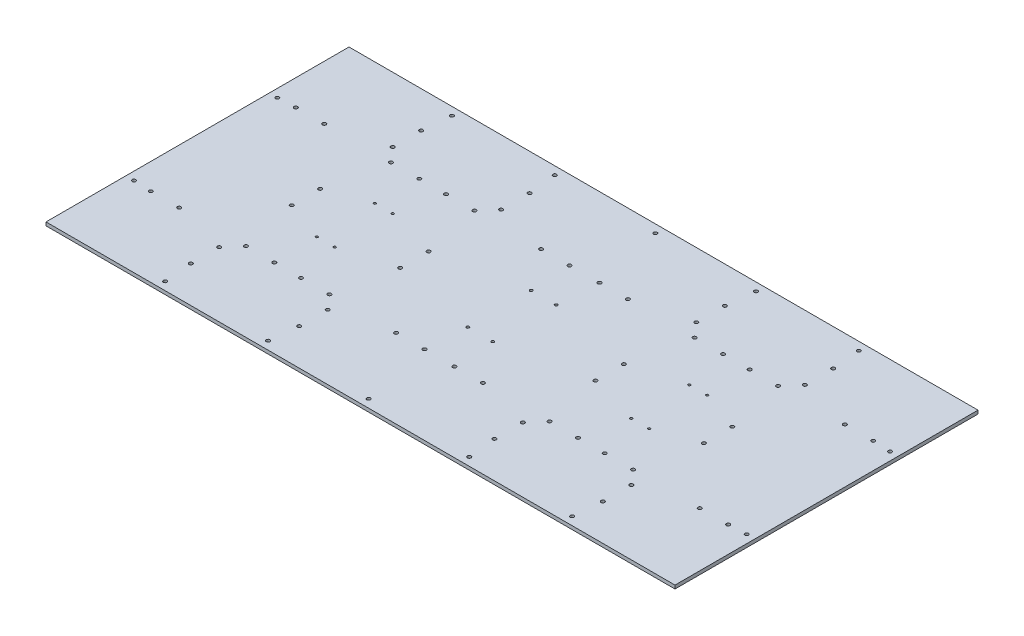
SolidWorks part; units mm, degrees
ref_plane "Front Plane" through (0, 0, 0) normal (0, 0, 1) x (1, 0, 0)
ref_plane "Top Plane" through (0, 0, 0) normal (0, 1, 0) x (1, 0, 0)
ref_plane "Right Plane" through (0, 0, 0) normal (1, 0, 0) x (0, 0, -1)
sketch "Sketch1" plane through (0, 0, 0) normal (0, 1, 0) x (1, 0, 0)
  line L0 (0, 139.7) -> (0, -139.7) construction
  line L1 (-290, 139.7) -> (290, 139.7)
  line L2 (-290, 139.7) -> (-290, -139.7)
  line L3 (-290, -139.7) -> (290, -139.7)
  line L4 (290, 139.7) -> (290, -139.7)
  line L5 (-290, 139.7) -> (290, -139.7) construction
  line L6 (-290, -139.7) -> (290, 139.7) construction
  line L7 (-282.5, 132.2) -> (282.5, 132.2) construction
  line L8 (-282.5, 132.2) -> (-282.5, -132.2) construction
  line L9 (-282.5, -132.2) -> (282.5, -132.2) construction
  line L10 (282.5, 132.2) -> (282.5, -132.2) construction
  line L11 (-282.5, 132.2) -> (282.5, -132.2) construction
  line L12 (-282.5, -132.2) -> (282.5, 132.2) construction
  line L13 (-290, 0) -> (290, 0) construction
  line L14 (282.5, 132.2) -> (282.5, -132.2) construction
  circle A0 centre (-282.5, 66.1) radius 1.65
  circle A1 centre (-187.6333, 132.2) radius 1.65
  circle A2 centre (-92.7667, 132.2) radius 1.65
  circle A3 centre (-282.5, -66.1) radius 1.65
  circle A4 centre (-92.7667, -132.2) radius 1.65
  circle A5 centre (-187.6333, -132.2) radius 1.65
  circle A6 centre (187.6333, -132.2) radius 1.65
  circle A7 centre (92.7667, -132.2) radius 1.65
  circle A8 centre (92.7667, 132.2) radius 1.65
  circle A9 centre (187.6333, 132.2) radius 1.65
  circle A10 centre (282.5, -66.1) radius 1.65
  circle A11 centre (282.5, 66.1) radius 1.65
  circle A12 centre (0, 132.2) radius 1.65
  circle A13 centre (0, -132.2) radius 1.65
  point P0 (0, 0)
  point P6 (0, 0)
  dimension "D5" = 3.3
  dimension "D6" = 3.3
  dimension "D7" = 3.3
  dimension "D12" = 3.3
  dimension "D13" = 3.3
  dimension "D1" = 580
  dimension "D2" = 279.4
  dimension "D3" = 7.5
  dimension "D4" = 7.5
  dimension "D8" = 66.1
  dimension "D9" = 94.8667
  dimension "D10" = 94.8667
  dimension "D11" = 92.7667
extrude "Boss-Extrude1" add sketch "Sketch1" along normal blind 3.175
sketch "Sketch2" plane through (0, 3.175, 0) normal (0, 1, 0) x (1, 0, 0)
  line L0 (0, 139.7) -> (0, -139.7) construction
  line L1 (290, 139.7) -> (-290, 139.7) construction
  line L2 (-290, -139.7) -> (290, -139.7) construction
  line L3 (-140, 139.7) -> (-140, -139.7) construction
  line L5 (-290, 0) -> (290, 0) construction
  line L6 (-290, 139.7) -> (-290, -139.7) construction
  line L7 (290, -139.7) -> (290, 139.7) construction
  line L8 (-190, 139.7) -> (-190, -139.7) construction
  circle A0 centre (-190, 13.1) radius 1.65
  circle A6 centre (-266.2, 66.8739) radius 1.65
  circle A7 centre (-240, 66.8739) radius 1.65
  circle A8 centre (-178.5, 66.8739) radius 1.65
  circle A9 centre (-152.3, 66.8739) radius 1.65
  circle A10 centre (-190, 106.2) radius 1.65
  circle A11 centre (-190, 80) radius 1.65
  circle A12 centre (-190, -80) radius 1.65
  circle A13 centre (-190, -106.2) radius 1.65
  circle A14 centre (-152.3, -66.8739) radius 1.65
  circle A15 centre (-178.5, -66.8739) radius 1.65
  circle A16 centre (-240, -66.8739) radius 1.65
  circle A17 centre (-266.2, -66.8739) radius 1.65
  circle A18 centre (-190, -13.1) radius 1.65
  circle A19 centre (-90, -13.1) radius 1.65
  circle A20 centre (-13.8, -66.8739) radius 1.65
  circle A21 centre (-40, -66.8739) radius 1.65
  circle A22 centre (-101.5, -66.8739) radius 1.65
  circle A23 centre (-127.7, -66.8739) radius 1.65
  circle A24 centre (-90, -106.2) radius 1.65
  circle A25 centre (-90, -80) radius 1.65
  circle A26 centre (-90, 80) radius 1.65
  circle A27 centre (-90, 106.2) radius 1.65
  circle A28 centre (-127.7, 66.8739) radius 1.65
  circle A29 centre (-101.5, 66.8739) radius 1.65
  circle A30 centre (-40, 66.8739) radius 1.65
  circle A31 centre (-13.8, 66.8739) radius 1.65
  circle A32 centre (-90, 13.1) radius 1.65
  circle A33 centre (90, 13.1) radius 1.65
  circle A34 centre (13.8, 66.8739) radius 1.65
  circle A35 centre (40, 66.8739) radius 1.65
  circle A36 centre (101.5, 66.8739) radius 1.65
  circle A37 centre (127.7, 66.8739) radius 1.65
  circle A38 centre (90, 106.2) radius 1.65
  circle A39 centre (90, 80) radius 1.65
  circle A40 centre (90, -80) radius 1.65
  circle A41 centre (90, -106.2) radius 1.65
  circle A42 centre (127.7, -66.8739) radius 1.65
  circle A43 centre (101.5, -66.8739) radius 1.65
  circle A44 centre (40, -66.8739) radius 1.65
  circle A45 centre (13.8, -66.8739) radius 1.65
  circle A46 centre (90, -13.1) radius 1.65
  circle A47 centre (190, -13.1) radius 1.65
  circle A48 centre (266.2, -66.8739) radius 1.65
  circle A49 centre (240, -66.8739) radius 1.65
  circle A50 centre (178.5, -66.8739) radius 1.65
  circle A51 centre (152.3, -66.8739) radius 1.65
  circle A52 centre (190, -106.2) radius 1.65
  circle A53 centre (190, -80) radius 1.65
  circle A54 centre (190, 80) radius 1.65
  circle A55 centre (190, 106.2) radius 1.65
  circle A56 centre (152.3, 66.8739) radius 1.65
  circle A57 centre (178.5, 66.8739) radius 1.65
  circle A58 centre (240, 66.8739) radius 1.65
  circle A59 centre (266.2, 66.8739) radius 1.65
  circle A60 centre (190, 13.1) radius 1.65
  dimension "D6" = 3.3
  dimension "D4" = 13.1
  dimension "D10" = 26.2
  dimension "D11" = 26.2
  dimension "D14" = 26.2
  dimension "D15" = 11.5
  dimension "D3" = 190
  dimension "D16" = 50
  dimension "D17" = 80
  dimension "D18" = 50
  dimension "D19" = 66.8739
extrude "Cut-Extrude1" cut sketch "Sketch2" against normal up to surface (3.175 mm away) up to face at (0, 0, 0)
sketch "Sketch3" plane through (0, 3.175, 0) normal (0, 1, 0) x (1, 0, 0)
  line L1 (-11.525, 29.25) -> (11.525, 29.25) construction
  line L2 (-11.525, 29.25) -> (-11.525, -29.25) construction
  line L3 (-11.525, -29.25) -> (11.525, -29.25) construction
  line L4 (11.525, 29.25) -> (11.525, -29.25) construction
  line L5 (-11.525, 29.25) -> (11.525, -29.25) construction
  line L6 (-11.525, -29.25) -> (11.525, 29.25) construction
  line L7 (-145, 139.7) -> (-145, -139.7) construction
  line L8 (290, 139.7) -> (-290, 139.7) construction
  line L9 (-290, -139.7) -> (290, -139.7) construction
  line L10 (0, 139.7) -> (0, -139.7) construction
  line L11 (-290, 139.7) -> (-290, -139.7) construction
  line L12 (153.25, -26.75) -> (136.75, 26.75) construction
  line L13 (-153.25, 26.75) -> (-136.75, 26.75) construction
  line L14 (-153.25, 26.75) -> (-153.25, -26.75) construction
  line L15 (-153.25, -26.75) -> (-136.75, -26.75) construction
  line L16 (-136.75, 26.75) -> (-136.75, -26.75) construction
  line L17 (-153.25, 26.75) -> (-136.75, -26.75) construction
  line L18 (-153.25, -26.75) -> (-136.75, 26.75) construction
  line L19 (153.25, 26.75) -> (136.75, -26.75) construction
  line L20 (136.75, 26.75) -> (136.75, -26.75) construction
  line L21 (153.25, -26.75) -> (136.75, -26.75) construction
  line L22 (153.25, 26.75) -> (153.25, -26.75) construction
  line L23 (153.25, 26.75) -> (136.75, 26.75) construction
  line L24 (145, 139.7) -> (145, -139.7) construction
  circle A0 centre (-11.525, 29.25) radius 1.3
  circle A1 centre (11.525, 29.25) radius 1.3
  circle A2 centre (11.525, -29.25) radius 1.3
  circle A3 centre (-11.525, -29.25) radius 1.3
  circle A4 centre (-153.25, 26.75) radius 1.1
  circle A5 centre (-136.75, 26.75) radius 1.1
  circle A6 centre (-136.75, -26.75) radius 1.1
  circle A7 centre (-153.25, -26.75) radius 1.1
  circle A8 centre (153.25, -26.75) radius 1.1
  circle A9 centre (136.75, -26.75) radius 1.1
  circle A10 centre (136.75, 26.75) radius 1.1
  circle A11 centre (153.25, 26.75) radius 1.1
  point P0 (0, 0)
  point P20 (-145, 0)
  point P39 (145, 0)
  dimension "D1" = 2.6
  dimension "D6" = 2.2
  dimension "D2" = 58.5
  dimension "D3" = 23.05
  dimension "D4" = 290
  dimension "D5" = 145
  dimension "D7" = 53.5
  dimension "D8" = 16.5
extrude "Cut-Extrude2" cut sketch "Sketch3" against normal up to surface (3.175 mm away) up to face at (-101.5, 0, 68.5239)
equation "\"D6@Sketch1\"=\"D5@Sketch1\""
equation "\"D7@Sketch1\"=\"D5@Sketch1\""
equation "\"D10@Sketch1\"=\"D9@Sketch1\""
equation "\"D12@Sketch1\"=\"D5@Sketch1\""
equation "\"D13@Sketch1\"=\"D5@Sketch1\""
equation "\"D11@Sketch2\"=\"D10@Sketch2\""
equation "\"D4@Sketch2\"=\"D10@Sketch2\"/2"
equation "\"D14@Sketch2\"=\"D10@Sketch2\""
equation "\"D5@Sketch3\"=\"D4@Sketch3\"/2"
